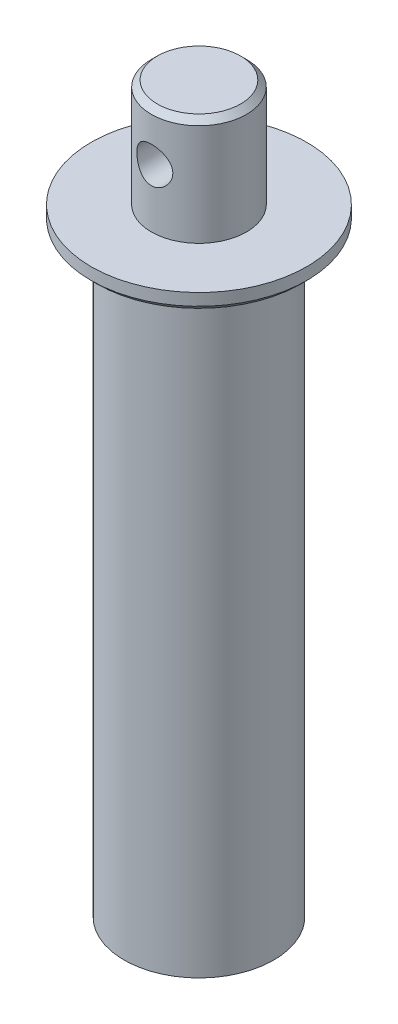
SolidWorks part; units mm, degrees
material "普通碳钢"
ref_plane "前视基准面" through (0, 0, 0) normal (0, 0, 1) x (1, 0, 0)
ref_plane "上视基准面" through (0, 0, 0) normal (0, 1, 0) x (1, 0, 0)
ref_plane "右视基准面" through (0, 0, 0) normal (1, 0, 0) x (0, 0, -1)
sketch "草图1" plane through (0, 0, 0) normal (0, 1, 0) x (1, 0, 0)
  circle A0 centre (0, 0) radius 7.95
  dimension "D1" = 15.9
extrude "凸台-拉伸1" add sketch "草图1" along normal blind 18 contours A0
chamfer "倒角2" distance 1 angle 45 1 edges at (0, 18, 7.95)
sketch "草图4" plane through (0, 0, 0) normal (0, 1, 0) x (1, 0, 0)
  circle A0 centre (0, 0) radius 18
extrude "凸台-拉伸2" add sketch "草图4" against normal blind 3
chamfer "倒角1" distance 1 angle 45 1 edges at (0, -3, 18)
ref_plane "基准面4" through (0, -3, 0) normal (0, -1, 0) x (-1, 0, 0)
sketch "草图5" plane through (0, -3, 0) normal (0, -1, 0) x (-1, 0, 0)
  circle A0 centre (0, 0) radius 12.5
extrude "凸台-拉伸3" add sketch "草图5" along normal blind 100
ref_plane "基准面5" through (0, -103, 0) normal (0, -1, 0) x (-1, 0, 0)
sketch "草图9" plane through (0, 0, 0) normal (0, 0, 1) x (1, 0, 0)
  line L0 (0, -19.8) -> (0, 19.8) construction
  line L1 (19.8, 0) -> (-19.8, 0) construction
  circle A0 centre (0, 9.7) radius 3
  dimension "D1" = 9.7
  dimension "D2" = 6
extrude "切除-拉伸2" cut sketch "草图9" against normal through all both and the other way through all
sketch "草图10" plane through (0, -3, 0) normal (0, -1, 0) x (-1, 0, 0)
  circle A0 centre (0, 0) radius 7.95
extrude "切除-拉伸3" cut sketch "草图10" along normal up to surface (100 mm away) from offset 10 up to face at (0, -103, -12.5)
